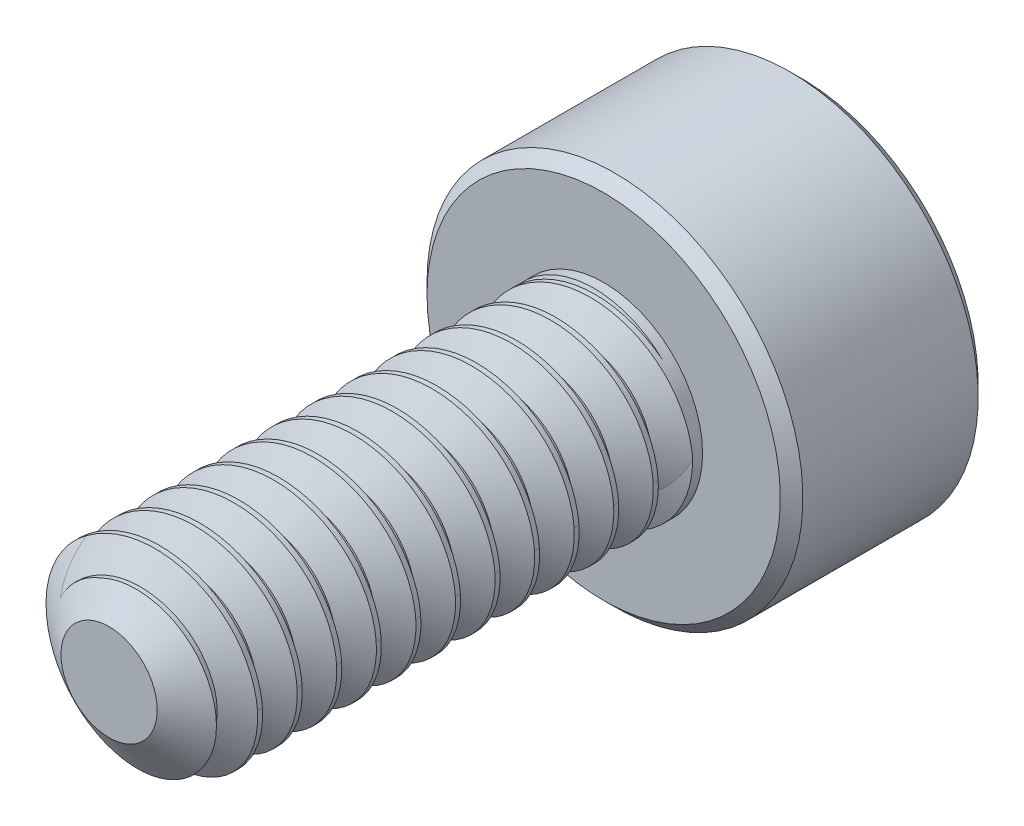
SolidWorks part; units mm, degrees
ref_plane "Front Plane" through (0, 0, 0) normal (0, 0, 1) x (1, 0, 0)
ref_plane "Top Plane" through (0, 0, 0) normal (0, 1, 0) x (1, 0, 0)
ref_plane "Right Plane" through (0, 0, 0) normal (1, 0, 0) x (0, 0, -1)
sketch "Sketch1" plane through (0, 0, 0) normal (0, 0, 1) x (1, 0, 0)
  circle A0 centre (0, 0) radius 1
  dimension "OD" = 2
extrude "Extrude1" add sketch "Sketch1" against normal blind 5
sketch "Sketch2" plane through (0, 0, 0) normal (0, 0, 1) x (1, 0, 0)
  circle A0 centre (0, 0) radius 1 construction
  circle A1 centre (0, 0) radius 1
curve "Helix/Spiral1" pitch 0.4 height 5.4 radius 1 centre (0, 0, 0) axis (0, 0, -1) start towards (0, 1, 0) parameters "pitch"=0.4
sketch "Sketch3" plane through (0, 0, 0) normal (1, 0, 0) x (0, 0, -1)
  line L0 (-0.35, 1) -> (-0.2, 0.7402)
  line L1 (-0.2, 0.7402) -> (-0.15, 0.7402)
  line L2 (-0.15, 0.7402) -> (0, 1)
  line L3 (-0.35, 1) -> (0, 1)
  line L4 (-0.175, 1) -> (-0.175, 0.7402) construction
  line L5 (-0.275, 0.8701) -> (-0.075, 0.8701) construction
  line L6 (0, 1) -> (0, -1) construction
  line L7 (0, -1) -> (5, -1) construction
  point P11 (1.8, -1)
  dimension "D1" = 0.05
  dimension "D2" = 0.2
  dimension "D3" = 60
  dimension "D4" = 1.8
sweep "Cut-Sweep1" cut profiles "Sketch3" path "Helix/Spiral1"
sketch "Sketch4" plane through (0, 0, 0) normal (1, 0, 0) x (0, 0, -1)
  line L0 (0.3598, 1) -> (0, 0.4862)
  line L1 (0, 0.4862) -> (0, 1)
  line L2 (0.3598, 1) -> (0, 1)
  line L3 (-0.35, 1) -> (0, 1) construction
  line L4 (0, 0) -> (7.0209, 0) construction
  dimension "D1" = 55
  dimension "D2" = 0.254
revolve "Cut-Revolve1" cut sketch "Sketch4" angle 360 about L4
sketch "Sketch5" plane through (0, 0, 0) normal (1, 0, 0) x (0, 0, -1)
  line L0 (5, -0.7135) -> (5, 0.7473) construction
  line L1 (5, 1) -> (0.1203, 1)
  line L2 (5, 1) -> (5, 0)
  line L3 (5, 0) -> (0.0001, 0)
  line L4 (0.0001, 0.6698) -> (0.0001, 0)
  line L5 (0.1203, 1) -> (0.0001, 0.6698)
  line L6 (0, 0) -> (9.9695, 0) construction
  point P3 (0.0001, 1)
  point P10 (0.0001, 1)
  dimension "D1" = 0.3302
  dimension "Thread min" = 0.0001
  dimension "D3" = 20
revolve "partially thread" [suppressed] add sketch "Sketch5" angle 360 about L6
sketch "Sketch6" plane through (0, 0, -5) normal (0, 0, -1) x (-1, 0, 0)
  circle A0 centre (0, 0) radius 1.9
  dimension "head dia" = 3.8
extrude "Extrude2" add sketch "Sketch6" along normal blind 2
sketch "Sketch7" plane through (0, 0, -7) normal (0, 0, -1) x (-1, 0, 0)
  line L1 (0, 0.866) -> (-0.75, 0.433)
  line L2 (-0.75, 0.433) -> (-0.75, -0.433)
  line L3 (-0.75, -0.433) -> (0, -0.866)
  line L4 (0, -0.866) -> (0.75, -0.433)
  line L5 (0.75, -0.433) -> (0.75, 0.433)
  line L6 (0.75, 0.433) -> (0, 0.866)
  circle A0 centre (0, 0) radius 0.75 construction
  dimension "hex dia" = 1.5
extrude "Cut-Extrude1" cut sketch "Sketch7" against normal blind 1.125
sketch "Sketch8" plane through (0, 0, -7) normal (0, 0, -1) x (-1, 0, 0)
  circle A0 centre (0, 0) radius 0.866
extrude "Cut-Extrude2" cut sketch "Sketch8" against normal through all draft 45
chamfer "Chamfer1" distance 0.114 angle 45 2 edges at (-1.9, 0, -7) (-1.9, 0, -5)
sketch "Sketch9" plane through (0, 0, 0) normal (1, 0, 0) x (0, 0, -1)
  line L0 (0, 1) -> (0, -1) construction
  line L1 (2.2, 1) -> (2.2, -1) construction
  dimension "D1" = 2.2
sketch "Sketch10" plane through (0, 0, 0) normal (1, 0, 0) x (0, 0, -1)
  line L0 (5, 1) -> (5, 0)
  line L1 (5, 1) -> (4.9, 1)
  line L2 (4.9, 1) -> (4.4858, 0)
  line L3 (5, 0) -> (4.4858, 0)
  line L4 (5, 1.786) -> (5, -1.786) construction
  dimension "D1" = 22.5
  dimension "D2" = 0.1
revolve "Revolve1" add sketch "Sketch10" angle 360 about L3
equation "\"D3@Helix/Spiral1\" = \"screw length@Extrude1\"+\"pitch@Helix/Spiral1\""
equation "\"D1@Sketch3\" = \"pitch@Helix/Spiral1\"*.125"
equation "\"D2@Sketch3\" = \"pitch@Helix/Spiral1\"*.5"
equation "\"D1@Cut-Extrude1\" = \"hex dia@Sketch7\"*.75"
equation "\"D1@Chamfer1\" = \"head dia@Sketch6\"*.03"
equation "\"D1@Sketch9\" = \"pitch@Helix/Spiral1\"*5.5"
equation "\"D2@Sketch10\" = \"pitch@Helix/Spiral1\"*.25"
equation "\"D4@Sketch3\" = \"pitch@Helix/Spiral1\"*4.50"
